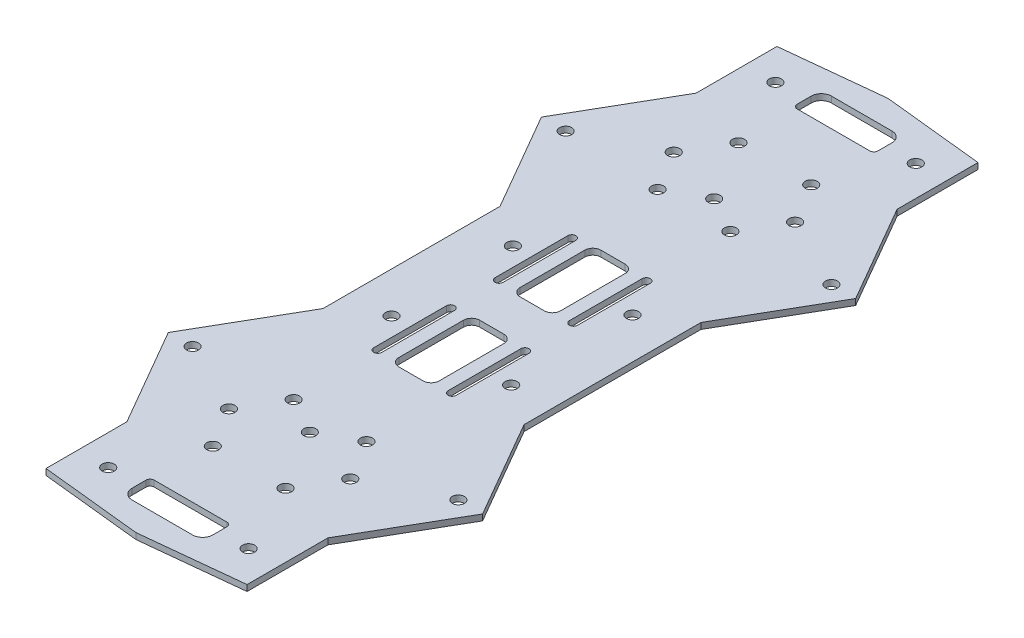
SolidWorks part; units mm, degrees
other "TopFrame"
ref_plane "Front Plane" through (0, 0, 0) normal (0, 0, 1) x (1, 0, 0)
ref_plane "Top Plane" through (0, 0, 0) normal (0, 1, 0) x (1, 0, 0)
ref_plane "Right Plane" through (0, 0, 0) normal (1, 0, 0) x (0, 0, -1)
sketch "Sketch1" plane through (0, 0, 0) normal (0, 1, 0) x (1, 0, 0)
  line L0 (-9.2, 6) -> (-9.2, 24) construction
  line L1 (-3, 5) -> (3, 5)
  line L2 (-5, 7) -> (-5, 23)
  line L3 (-3, 25) -> (3, 25)
  line L4 (5, 7) -> (5, 23)
  line L5 (-5, 5) -> (5, 25) construction
  line L6 (-5, 25) -> (5, 5) construction
  line L11 (-10.2, 6) -> (-10.2, 24)
  line L12 (-8.2, 6) -> (-8.2, 24)
  line L13 (0, 5) -> (0, 25) construction
  line L14 (9.2, 6) -> (9.2, 24) construction
  line L15 (10.2, 6) -> (10.2, 24)
  line L16 (8.2, 6) -> (8.2, 24)
  line L17 (-3, 0) -> (3, 0) construction
  line L18 (0, -5) -> (0, -25) construction
  line L19 (-5, -25) -> (5, -5) construction
  line L20 (-5, -5) -> (5, -25) construction
  line L21 (5, -7) -> (5, -23)
  line L22 (-3, -25) -> (3, -25)
  line L23 (-5, -7) -> (-5, -23)
  line L24 (-3, -5) -> (3, -5)
  line L25 (9.2, -6) -> (9.2, -24) construction
  line L26 (10.2, -6) -> (10.2, -24)
  line L27 (8.2, -6) -> (8.2, -24)
  line L28 (-9.2, -6) -> (-9.2, -24) construction
  line L29 (-10.2, -6) -> (-10.2, -24)
  line L30 (-8.2, -6) -> (-8.2, -24)
  line L31 (0, 93) -> (-24.863, 90.3868)
  line L32 (-24.863, 90.3868) -> (-24.863, 70.3868)
  line L33 (-24.863, 70.3868) -> (-38.863, 46.1381)
  line L34 (-38.863, 46.1381) -> (-24.863, 21.8894)
  line L35 (-24.863, 21.8894) -> (-24.863, -21.8894)
  line L36 (24.863, 21.8894) -> (24.863, -21.8894)
  line L37 (38.863, 46.1381) -> (24.863, 21.8894)
  line L38 (24.863, 70.3868) -> (38.863, 46.1381)
  line L39 (24.863, 90.3868) -> (24.863, 70.3868)
  line L40 (0, 93) -> (24.863, 90.3868)
  line L41 (0, -93) -> (24.863, -90.3868)
  line L42 (24.863, -90.3868) -> (24.863, -70.3868)
  line L43 (24.863, -70.3868) -> (38.863, -46.1381)
  line L44 (38.863, -46.1381) -> (24.863, -21.8894)
  line L45 (-38.863, -46.1381) -> (-24.863, -21.8894)
  line L46 (-24.863, -70.3868) -> (-38.863, -46.1381)
  line L47 (-24.863, -90.3868) -> (-24.863, -70.3868)
  line L48 (0, -93) -> (-24.863, -90.3868)
  arc A0 (-3, 5) -> (-5, 7) centre (-3, 7) cw
  arc A1 (3, 5) -> (5, 7) centre (3, 7) ccw
  arc A2 (3, 25) -> (5, 23) centre (3, 23) cw
  arc A3 (-5, 23) -> (-3, 25) centre (-3, 23) cw
  arc A4 (-10.2, 6) -> (-8.2, 6) centre (-9.2, 6) ccw
  arc A5 (-8.2, 24) -> (-10.2, 24) centre (-9.2, 24) ccw
  arc A6 (10.2, 6) -> (8.2, 6) centre (9.2, 6) cw
  arc A7 (8.2, 24) -> (10.2, 24) centre (9.2, 24) cw
  arc A8 (-5, -23) -> (-3, -25) centre (-3, -23) ccw
  arc A9 (3, -25) -> (5, -23) centre (3, -23) ccw
  arc A10 (3, -5) -> (5, -7) centre (3, -7) cw
  arc A11 (-3, -5) -> (-5, -7) centre (-3, -7) ccw
  arc A12 (10.2, -6) -> (8.2, -6) centre (9.2, -6) ccw
  arc A13 (8.2, -24) -> (10.2, -24) centre (9.2, -24) ccw
  arc A14 (-10.2, -6) -> (-8.2, -6) centre (-9.2, -6) cw
  arc A15 (-8.2, -24) -> (-10.2, -24) centre (-9.2, -24) cw
  circle A16 centre (0, 50) radius 1.5
  circle A17 centre (-9, 45) radius 1.5
  circle A18 centre (-15, 55) radius 1.5
  circle A19 centre (-9, 65) radius 1.5
  circle A20 centre (9, 45) radius 1.5
  circle A21 centre (9, 65) radius 1.5
  circle A22 centre (15, 55) radius 1.5
  circle A23 centre (-14.8, 15) radius 1.5
  circle A24 centre (14.8, 15) radius 1.5
  circle A25 centre (-32.863, 46.1381) radius 1.5
  circle A26 centre (-17.363, 82.5) radius 1.5
  circle A27 centre (32.863, 46.1381) radius 1.5
  circle A28 centre (17.363, 82.5) radius 1.5
  circle A29 centre (-14.8, -15) radius 1.5
  circle A30 centre (14.8, -15) radius 1.5
  circle A31 centre (32.863, -46.1381) radius 1.5
  circle A32 centre (9, -45) radius 1.5
  circle A33 centre (-32.863, -46.1381) radius 1.5
  circle A34 centre (-9, -45) radius 1.5
  circle A35 centre (15, -55) radius 1.5
  circle A36 centre (0, -50) radius 1.5
  circle A37 centre (-15, -55) radius 1.5
  circle A38 centre (-9, -65) radius 1.5
  circle A39 centre (9, -65) radius 1.5
  circle A40 centre (17.363, -82.5) radius 1.5
  circle A41 centre (-17.363, -82.5) radius 1.5
  point P0 (0, 15)
  point P19 (-9.2, 15)
  point P25 (-9.2, 25)
  point P26 (-9.2, 5)
  point P31 (9.2, 15)
  point P58 (9.2, -15)
  point P65 (-9.2, -15)
  point P70 (0, -15)
  point P83 (24.863, 0)
  point P84 (-24.863, 0)
  dimension "D4" = 2
  dimension "D6" = 1
  dimension "D15" = 3
  dimension "D16" = 25
  dimension "D17" = 20
  dimension "D18" = 9
  dimension "D19" = 10
  dimension "D21" = 10
  dimension "D23" = 3
  dimension "D24" = 3
  dimension "D25" = 3
  dimension "D26" = 4.6
  dimension "D27" = 3
  dimension "D28" = 6
  dimension "D29" = 3
  dimension "D30" = 7.5
  dimension "D31" = 3
  dimension "D32" = 57.5
  dimension "D1" = 10
  dimension "D2" = 20
  dimension "D3" = 5
  dimension "D5" = 20
  dimension "D7" = 3.2
  dimension "D8" = 25
  dimension "D9" = 68
  dimension "D10" = 20
  dimension "D11" = 96
  dimension "D12" = 28
  dimension "D13" = 150
  dimension "D14" = 120
  dimension "D20" = 6
  dimension "D22" = 6
extrude "Boss-Extrude1" add sketch "Sketch1" along normal blind 1.5
sketch "Sketch2" plane through (0, 1.5, 0) normal (0, 1, 0) x (1, 0, 0)
  line L0 (0, 0) -> (9, 0) construction
  line L1 (-9, 79.5) -> (9, 79.5)
  line L2 (-10, 80.5) -> (-10, 84)
  line L3 (-7.5, 86.5) -> (7.5, 86.5)
  line L4 (10, 80.5) -> (10, 84)
  line L5 (-10, 79.5) -> (10, 86.5) construction
  line L6 (-10, 86.5) -> (10, 79.5) construction
  line L7 (-10, -86.5) -> (10, -79.5) construction
  line L8 (-10, -79.5) -> (10, -86.5) construction
  line L9 (10, -80.5) -> (10, -84)
  line L10 (-7.5, -86.5) -> (7.5, -86.5)
  line L11 (-10, -80.5) -> (-10, -84)
  line L12 (-9, -79.5) -> (9, -79.5)
  arc A0 (9, 79.5) -> (10, 80.5) centre (9, 80.5) ccw
  arc A1 (-9, 79.5) -> (-10, 80.5) centre (-9, 80.5) cw
  arc A2 (7.5, 86.5) -> (10, 84) centre (7.5, 84) cw
  arc A3 (-10, 84) -> (-7.5, 86.5) centre (-7.5, 84) cw
  arc A4 (-10, -84) -> (-7.5, -86.5) centre (-7.5, -84) ccw
  arc A5 (7.5, -86.5) -> (10, -84) centre (7.5, -84) ccw
  arc A6 (-9, -79.5) -> (-10, -80.5) centre (-9, -80.5) ccw
  arc A7 (9, -79.5) -> (10, -80.5) centre (9, -80.5) cw
  point P0 (0, 83)
  point P36 (0, -83)
  dimension "D3" = 1
  dimension "D5" = 2.5
  dimension "D1" = 20
  dimension "D2" = 7
  dimension "D4" = 79.5
extrude "Cut-Extrude1" cut sketch "Sketch2" against normal up to surface (1.5 mm away) up to face at (17.363, 0, 84)
